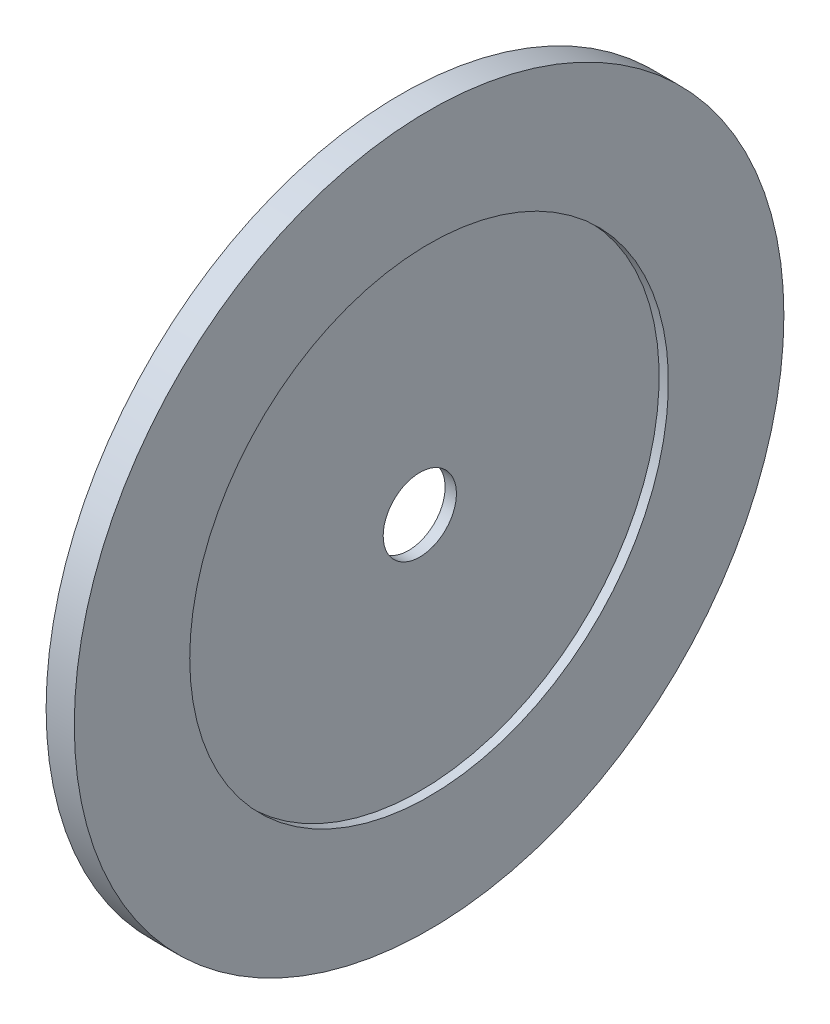
SolidWorks part; units mm, degrees
ref_plane "Front Plane" through (0, 0, 0) normal (0, 0, 1) x (1, 0, 0)
ref_plane "Top Plane" through (0, 0, 0) normal (0, 1, 0) x (1, 0, 0)
ref_plane "Right Plane" through (0, 0, 0) normal (1, 0, 0) x (0, 0, -1)
sketch "Sketch1" plane through (0, 0, 0) normal (0, 0, 1) x (1, 0, 0)
  line L0 (0, 0) -> (58.591, 0) construction
  line L2 (0, 0) -> (19, 0)
  line L3 (0, 0) -> (0, 2.5)
  line L4 (0, 2.5) -> (19, 2.5)
  line L5 (19, 0) -> (19, 2.5)
  line L6 (6.7938, 2.5) -> (6.7938, 6)
  line L11 (6.7938, 6) -> (10.7938, 6)
  line L16 (12.8938, 6) -> (12.8938, 3)
  line L17 (12.8938, 3) -> (13.8938, 3)
  line L18 (13.8938, 3) -> (13.8938, 2.5)
  line L19 (13.8938, 2.5) -> (6.7938, 2.5)
  line L22 (13.8938, 2.5) -> (16.3938, 2.5)
  line L23 (13.8938, 2.5) -> (13.8938, 4)
  line L24 (13.8938, 4) -> (16.3938, 4)
  line L25 (16.3938, 2.5) -> (16.3938, 4)
  line L27 (6.7938, 6) -> (10.7938, 6)
  line L28 (6.7938, 6) -> (6.7938, 9)
  line L29 (6.7938, 9) -> (10.7938, 9)
  line L30 (10.7938, 6) -> (10.7938, 9)
  line L31 (6.7938, 9) -> (6.7938, 8.5)
  line L32 (6.7938, 8.5) -> (5, 8.5)
  line L33 (7.8969, 22.001) -> (7.8969, 12.476) construction
  line L34 (5, 12.476) -> (10.7938, 12.476)
  line L35 (10.7938, 12.476) -> (10.7938, 9)
  line L36 (5, 7.5) -> (3, 7.5)
  line L37 (5, 8.5) -> (5, 12.476)
  line L38 (5, 7.5) -> (5, 14)
  line L39 (5, 14) -> (3, 14)
  line L40 (3, 7.5) -> (3, 14)
  line L41 (5, 22.001) -> (10.7938, 22.001)
  line L42 (5, 22.001) -> (5, 30.1625)
  line L43 (5, 30.1625) -> (10.7938, 30.1625)
  line L44 (10.7938, 22.001) -> (10.7938, 30.1625)
  line L45 (13.8938, 4) -> (13.8938, 22.001)
  line L49 (16.8938, 22.001) -> (16.8938, 8)
  line L50 (16.8938, 8) -> (17.8938, 8)
  line L51 (22.8938, 7.5) -> (22.8938, 6.5)
  line L54 (16.3938, 4) -> (13.8938, 4)
  line L55 (17.8938, 8) -> (17.8938, 7.5)
  line L56 (17.8938, 7.5) -> (22.8938, 7.5)
  line L57 (13.8938, 22.001) -> (16.8938, 22.001)
  line L58 (16.3938, 3.5) -> (19.8938, 3.5)
  line L59 (28.8938, 14) -> (26.3938, 11.5)
  line L60 (4, 31.75) -> (17.8938, 31.75)
  line L61 (17.8938, 7.5) -> (22.8938, 7.5)
  line L62 (17.8938, 7.5) -> (17.8938, 12)
  line L63 (17.8938, 12) -> (22.8938, 12)
  line L64 (22.8938, 7.5) -> (22.8938, 12)
  line L65 (17.8938, 31.75) -> (17.8938, 12)
  line L66 (22.8938, 11.5) -> (26.3938, 11.5)
  line L67 (32.8938, 23) -> (29.8938, 20)
  line L68 (33.8938, 31.5) -> (36.0538, 33.66)
  line L69 (28.8938, 14) -> (28.8938, 15)
  line L70 (28.8938, 15) -> (21.8938, 15)
  line L71 (21.8938, 15) -> (21.8938, 16)
  line L72 (21.8938, 16) -> (20.8938, 16)
  line L73 (20.8938, 16) -> (20.8938, 41)
  line L74 (19.8938, 40) -> (9.8938, 40)
  line L75 (9.8938, 40) -> (4, 40)
  line L76 (20.8938, 41) -> (19.8938, 41)
  line L77 (21.8938, 15) -> (28.8938, 15)
  line L78 (21.8938, 15) -> (21.8938, 21)
  line L79 (21.8938, 21) -> (28.8938, 21)
  line L80 (28.8938, 15) -> (28.8938, 21)
  line L81 (9.8938, 40) -> (19.8938, 40)
  line L82 (9.8938, 40) -> (9.8938, 50)
  line L83 (9.8938, 50) -> (19.8938, 50)
  line L84 (19.8938, 40) -> (19.8938, 50)
  line L85 (4, 40) -> (4, 31.75)
  line L87 (29.8938, 20) -> (28.8938, 20)
  line L88 (21.8938, 21) -> (21.8938, 63.001)
  line L89 (21.8938, 63.001) -> (24.8938, 63.001)
  line L90 (24.8938, 63.001) -> (24.8938, 26)
  line L91 (24.8938, 26) -> (25.8938, 26)
  line L92 (9.8938, 49) -> (8.65, 49)
  line L93 (8.65, 49) -> (8.65, 53.476)
  line L94 (8.65, 53.476) -> (19.8938, 53.476)
  line L95 (19.8938, 53.476) -> (19.8938, 50)
  line L96 (14.2719, 63.001) -> (14.2719, 53.476) construction
  line L97 (8.65, 63.001) -> (19.8938, 63.001)
  line L98 (8.65, 63.001) -> (8.65, 68.2625)
  line L99 (8.65, 68.2625) -> (19.8938, 68.2625)
  line L100 (19.8938, 63.001) -> (19.8938, 68.2625)
  line L101 (12.8938, 6) -> (11.8938, 6)
  line L102 (8.65, 42.5) -> (4.65, 42.5)
  line L103 (8.65, 42.5) -> (8.65, 55)
  line L104 (8.65, 55) -> (4.65, 55)
  line L105 (4.65, 42.5) -> (4.65, 55)
  line L106 (25.8938, 26) -> (25.8938, 25)
  line L107 (25.8938, 25) -> (32.8938, 25)
  line L108 (32.8938, 25) -> (32.8938, 23)
  line L109 (0, 0) -> (-2, 0)
  line L110 (0, 0) -> (0, 11)
  line L111 (25.8938, 25) -> (32.8938, 25)
  line L112 (25.8938, 25) -> (25.8938, 32.5)
  line L113 (25.8938, 32.5) -> (32.8938, 32.5)
  line L114 (32.8938, 25) -> (32.8938, 32.5)
  line L115 (33.8938, 31.5) -> (32.8938, 31.5)
  line L116 (25.8938, 32.5) -> (25.8938, 69.85)
  line L117 (25.8938, 69.85) -> (-1.35, 69.85)
  line L118 (-1.35, 69.85) -> (-1.35, 76.2)
  line L119 (-1.35, 76.2) -> (27.7938, 76.2)
  line L120 (0, 11) -> (-2, 11)
  line L121 (36.0538, 53.975) -> (28.1163, 53.975)
  line L123 (27.7938, 76.2) -> (36.0538, 67.94)
  line L124 (36.0538, 67.94) -> (36.0538, 33.66)
  line L125 (-2, 0) -> (-2, 11)
  line L126 (36.0538, 47.625) -> (28.1163, 47.625)
  line L127 (28.1163, 53.975) -> (28.1163, 47.625)
  line L129 (-0.35, 63.001) -> (-0.35, 31)
  line L132 (4.65, 63.001) -> (-0.35, 63.001)
  line L134 (-0.35, 31) -> (-1.35, 31)
  line L135 (-1.35, 31) -> (-1.35, 30)
  line L136 (-1.35, 30) -> (-11.35, 30)
  line L137 (-11.35, 30) -> (-11.35, 25.4)
  line L138 (-11.35, 25.4) -> (-2, 25.4)
  line L139 (-2, 25.4) -> (-2, 11.5)
  line L140 (-1.35, 76.2) -> (-4.35, 76.2)
  line L141 (-1.35, 30) -> (-11.35, 30)
  line L142 (-1.35, 30) -> (-1.35, 39)
  line L143 (-1.35, 39) -> (-11.35, 39)
  line L144 (-11.35, 30) -> (-11.35, 39)
  line L145 (-4.35, 76.2) -> (-12.35, 68.2)
  line L146 (-12.35, 68.2) -> (-12.35, 38)
  line L147 (-12.35, 38) -> (-11.35, 38)
  line L148 (-1.35, 39) -> (-1.35, 69.85)
  line L149 (11.8938, 6) -> (11.8938, 5.45)
  line L154 (-2, 11.5) -> (1, 11.5)
  line L155 (4.65, 60.6197) -> (23.7, 60.6197)
  line L160 (4.65, 60.6197) -> (4.65, 55.8572)
  line L161 (4.65, 55.8572) -> (23.7, 55.8572)
  line L166 (23.7, 60.6197) -> (23.7, 55.8572)
  line L167 (4.65, 60.6197) -> (23.7, 55.8572) construction
  line L172 (4.65, 55.8572) -> (23.7, 60.6197) construction
  line L173 (23.7, 62.2072) -> (24.8938, 62.2072)
  line L174 (11.8938, 5.45) -> (10.7938, 5.45)
  line L175 (10.7938, 5.45) -> (10.7938, 6)
  line L176 (23.7, 62.2072) -> (23.7, 54.2697)
  line L177 (23.7, 54.2697) -> (24.8938, 54.2697)
  line L178 (24.8938, 62.2072) -> (24.8938, 54.2697)
  line L179 (23.7, 62.2072) -> (24.8938, 54.2697) construction
  line L180 (23.7, 54.2697) -> (24.8938, 62.2072) construction
  line L181 (3, 19.6197) -> (15.7, 19.6197)
  line L182 (3, 19.6197) -> (3, 14.8572)
  line L183 (3, 14.8572) -> (15.7, 14.8572)
  line L184 (15.7, 19.6197) -> (15.7, 14.8572)
  line L185 (3, 19.6197) -> (15.7, 14.8572) construction
  line L186 (3, 14.8572) -> (15.7, 19.6197) construction
  line L187 (15.7, 21.2072) -> (16.8938, 21.2072)
  line L188 (15.7, 21.2072) -> (15.7, 13.2697)
  line L189 (15.7, 13.2697) -> (16.8938, 13.2697)
  line L190 (16.8938, 21.2072) -> (16.8938, 13.2697)
  line L191 (15.7, 21.2072) -> (16.8938, 13.2697) construction
  line L192 (15.7, 13.2697) -> (16.8938, 21.2072) construction
  line L193 (1, 11.5) -> (1, 6.5)
  line L194 (1, 6.5) -> (3, 6.5)
  line L195 (22.8938, 6.5) -> (19.8938, 3.5)
  line L196 (4.65, 63.001) -> (4.65, 42.5)
  line L197 (4.65, 42.5) -> (3, 42.5)
  line L198 (3, 42.5) -> (3, 6.5)
  point P7 (24.2969, 58.2385)
  point P131 (16.2969, 17.2385)
  point P135 (14.175, 58.2385)
  point P146 (9.35, 17.2385)
sketch "Sketch2" plane through (0, 0, 0) normal (0, 0, 1) x (1, 0, 0)
  line L0 (-1.35, 30) -> (-11.35, 30) construction
  line L1 (-2, 25.4) -> (-2, 11.5) construction
  line L2 (-11.35, 30) -> (-11.35, 25.4) construction
  line L3 (-11.35, 25.4) -> (-2, 25.4) construction
  line L4 (-2, 11.5) -> (1, 11.5) construction
  line L5 (1, 11.5) -> (1, 6.5) construction
  line L6 (1, 6.5) -> (3, 6.5) construction
  line L7 (3, 42.5) -> (3, 6.5) construction
  line L8 (4.65, 42.5) -> (3, 42.5) construction
  line L9 (4.65, 63.001) -> (4.65, 42.5) construction
  line L10 (4.65, 63.001) -> (-0.35, 63.001) construction
  line L11 (-0.35, 63.001) -> (-0.35, 31) construction
  line L12 (-0.35, 31) -> (-1.35, 31) construction
  line L13 (-1.35, 31) -> (-1.35, 30) construction
  line L14 (-1.35, 30) -> (-11.35, 30)
  line L15 (-2, 25.4) -> (-2, 11.5)
  line L16 (-11.35, 30) -> (-11.35, 25.4)
  line L17 (-11.35, 25.4) -> (-2, 25.4)
  line L18 (-2, 11.5) -> (1, 11.5)
  line L19 (1, 11.5) -> (1, 6.5)
  line L20 (1, 6.5) -> (3, 6.5)
  line L21 (3, 42.5) -> (3, 6.5)
  line L22 (4.65, 42.5) -> (3, 42.5)
  line L23 (4.65, 63.001) -> (4.65, 42.5)
  line L24 (4.65, 63.001) -> (-0.35, 63.001)
  line L25 (-0.35, 63.001) -> (-0.35, 31)
  line L26 (-0.35, 31) -> (-1.35, 31)
  line L27 (-1.35, 31) -> (-1.35, 30)
revolve "Revolve1" add sketch "Sketch2" angle 360 about L0 region at (0.1863, 34.915, 0)
